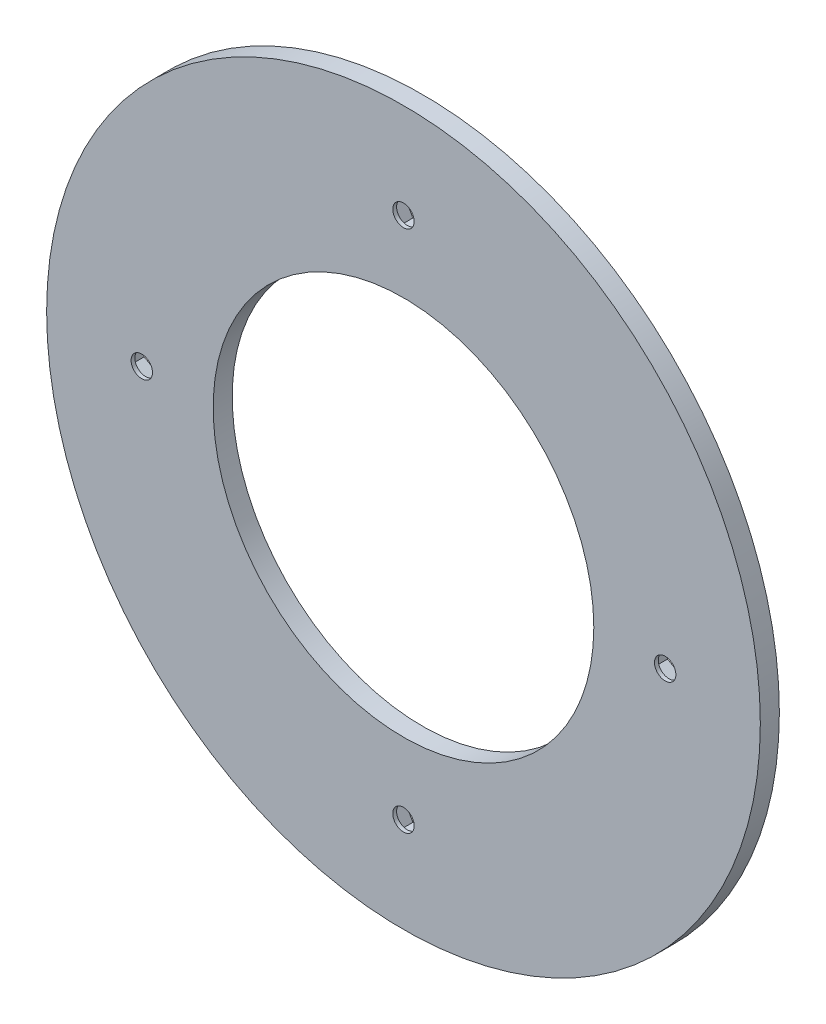
SolidWorks part; units mm, degrees
material "PET"
ref_plane "Front Plane" through (0, 0, 0) normal (0, 0, 1) x (1, 0, 0)
ref_plane "Top Plane" through (0, 0, 0) normal (0, 1, 0) x (1, 0, 0)
ref_plane "Right Plane" through (0, 0, 0) normal (1, 0, 0) x (0, 0, -1)
sketch "Sketch1" plane through (0, 0, 0) normal (0, 0, 1) x (1, 0, 0)
  circle A0 centre (0, 0) radius 75
  circle A1 centre (0, 0) radius 40
  dimension "D1" = 150
  dimension "D2" = 35
extrude "Boss-Extrude1" add sketch "Sketch1" along normal blind 4
sketch "Sketch2" plane through (0, 0, 4) normal (0, 0, 1) x (1, 0, 0)
  circle A0 centre (0, 0) radius 73
  circle A1 centre (0, 0) radius 75
  circle A2 centre (0, 0) radius 75
  dimension "D1" = 0
  dimension "D2" = 2
extrude "Boss-Extrude2" [suppressed] add sketch "Sketch2" along normal blind 8
sketch "Sketch3" [suppressed] plane through (0, 0, 0) normal (0, 1, 0) x (1, 0, 0)
  line L0 (-75, -12) -> (75, -12) construction
  circle A0 centre (0, -7) radius 1.5
  dimension "D2" = 3
  dimension "D1" = 5
extrude "Cut-Extrude1" [suppressed] cut sketch "Sketch3" against normal up to surface (75 mm away) up to face at (75, 0, 4)
pattern_circular "CirPattern1" [suppressed] count 4 over 360 of bodies 103
sketch "Sketch9" plane through (0, 0, 0) normal (0, 0, -1) x (-1, 0, 0)
  point P0 (0, 55)
  point P4 (55, 0)
  point P6 (0, -55)
  point P8 (-55, 0)
  dimension "D1" = 55
  dimension "D2" = 0
  dimension "D3" = 55
  dimension "D4" = 55
  dimension "D5" = 55
hole_wizard "M4 Clearance Hole1" positions "Sketch9" profile "Sketch10" hole size "M4" standard "ISO" end condition through all
sketch "Sketch10" plane through (0, 55, 0) normal (1, 0, 0) x (0, 1, 0)
  line L0 (0, 0) -> (0, 4)
  line L1 (0, 4) -> (2.25, 4)
  line L2 (2.25, 4) -> (2.25, 0)
  line L5 (2.25, 0) -> (0, 0)
  line L11 (0, -6.35) -> (0, 107.95) construction
  dimension "Thru Hole Dia." = 4.5
  dimension "Thru Hole Depth" = 4
sketch "Sketch13" plane through (0, 0, 0) normal (0, 0, -1) x (-1, 0, 0)
  line L0 (0, 0) -> (55, 0) construction
  line L1 (4.0415, 55) -> (2.0207, 58.5)
  line L2 (2.0207, 58.5) -> (-2.0207, 58.5)
  line L3 (-2.0207, 58.5) -> (-4.0415, 55)
  line L4 (-4.0415, 55) -> (-2.0207, 51.5)
  line L5 (-2.0207, 51.5) -> (2.0207, 51.5)
  line L6 (2.0207, 51.5) -> (4.0415, 55)
  line L7 (55, -4.0415) -> (58.5, -2.0207)
  line L8 (58.5, -2.0207) -> (58.5, 2.0207)
  line L9 (58.5, 2.0207) -> (55, 4.0415)
  line L10 (55, 4.0415) -> (51.5, 2.0207)
  line L11 (51.5, 2.0207) -> (51.5, -2.0207)
  line L12 (51.5, -2.0207) -> (55, -4.0415)
  line L13 (-4.0415, -55) -> (-2.0207, -58.5)
  line L14 (-2.0207, -58.5) -> (2.0207, -58.5)
  line L15 (2.0207, -58.5) -> (4.0415, -55)
  line L16 (4.0415, -55) -> (2.0207, -51.5)
  line L17 (2.0207, -51.5) -> (-2.0207, -51.5)
  line L18 (-2.0207, -51.5) -> (-4.0415, -55)
  line L19 (-55, 4.0415) -> (-58.5, 2.0207)
  line L20 (-58.5, 2.0207) -> (-58.5, -2.0207)
  line L21 (-58.5, -2.0207) -> (-55, -4.0415)
  line L22 (-55, -4.0415) -> (-51.5, -2.0207)
  line L23 (-51.5, -2.0207) -> (-51.5, 2.0207)
  line L24 (-51.5, 2.0207) -> (-55, 4.0415)
  circle A0 centre (0, 55) radius 3.5 construction
  circle A1 centre (55, 0) radius 3.5 construction
  circle A2 centre (0, -55) radius 3.5 construction
  circle A3 centre (-55, 0) radius 3.5 construction
  point P40 (0, 0)
  dimension "D1" = 7
extrude "Cut-Extrude2" cut sketch "Sketch13" against normal blind 3.2
sketch "Sketch14" plane through (0, 0, 0) normal (0, 0, -1) x (-1, 0, 0)
  point P0 (0, 0)
ref_point "Point2"
